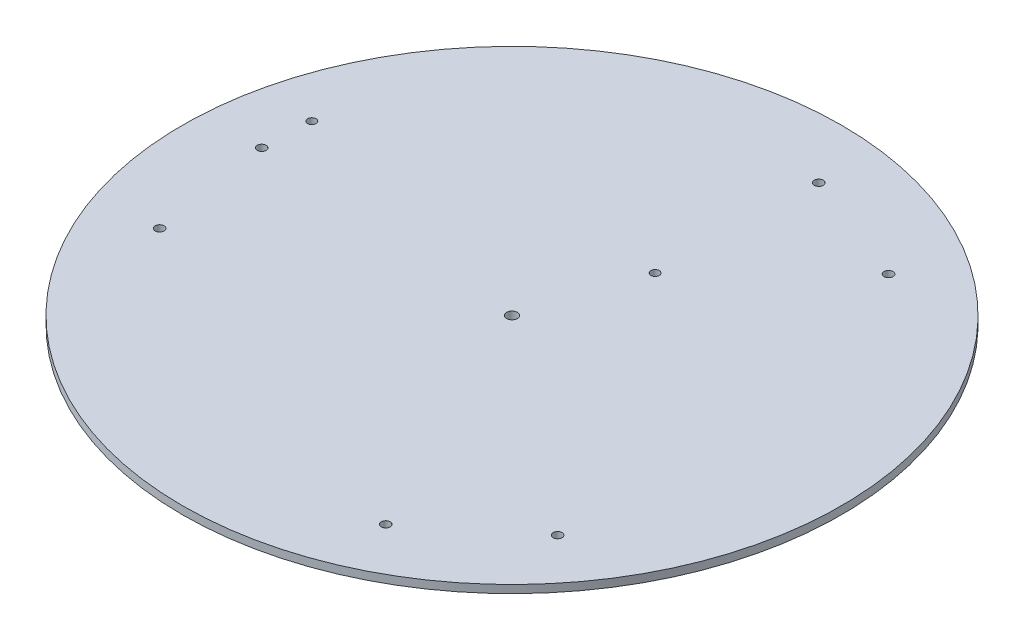
SolidWorks part; units mm, degrees
ref_plane "Front Plane" through (0, 0, 0) normal (0, 0, 1) x (1, 0, 0)
ref_plane "Top Plane" through (0, 0, 0) normal (0, 1, 0) x (1, 0, 0)
ref_plane "Right Plane" through (0, 0, 0) normal (1, 0, 0) x (0, 0, -1)
sketch "Sketch2" plane through (0, 0, 0) normal (0, 1, 0) x (1, 0, 0)
  circle A0 centre (0, 0) radius 125
  dimension "D1" = 250
extrude "Boss-Extrude1" add sketch "Sketch2" along normal blind 3
sketch "Sketch3" plane through (0, 3, 0) normal (0, 1, 0) x (1, 0, 0)
  line L4 (74.6446, 100.2656) -> (65.4599, 76.5843) construction
  line L5 (0, 0) -> (43.5629, 112.3204) construction
  line L6 (74.6446, 100.2656) -> (12.4813, 124.3753) construction
  line L7 (12.4813, 124.3753) -> (3.2966, 100.6941) construction
  line L8 (65.4599, 76.5843) -> (3.2966, 100.6941) construction
  circle A0 centre (0, 0) radius 125 construction
  circle A7 centre (57.8244, 84.9944) radius 1.7
  circle A8 centre (14.6061, 101.7564) radius 1.7
  circle A9 centre (44.6952, -92.5746) radius 1.7
  circle A10 centre (80.8206, -63.5274) radius 1.7
  circle A11 centre (-102.5195, 7.5802) radius 1.7
  circle A12 centre (-95.4267, -38.229) radius 1.7
  point P22 (0, 0)
  point P23 (0.4661, 0.2121)
  dimension "D2" = 3.4
  dimension "D1" = 25.4
  dimension "D3" = 5.08
  dimension "D5" = 66.675
  dimension "D6" = 3
  dimension "D4" = 10.16
extrude "Cut-Extrude1" cut sketch "Sketch3" against normal blind 26 and the other way blind 62
sketch "Sketch4" plane through (0, 3, 0) normal (0, 1, 0) x (1, 0, 0)
  circle A0 centre (0, 0) radius 2.05
  dimension "D1" = 4.1
extrude "Cut-Extrude2" cut sketch "Sketch4" against normal blind 33 and the other way blind 55
sketch "Sketch5" plane through (0, 0, 0) normal (0, -1, 0) x (1, 0, 0)
  circle A0 centre (-101.7781, -25.8548) radius 1.6
  circle A1 centre (13.2168, -41.0922) radius 1.6
  dimension "D1" = 3.2
  dimension "D2" = 3.2
extrude "Cut-Extrude3" cut sketch "Sketch5" against normal through all
